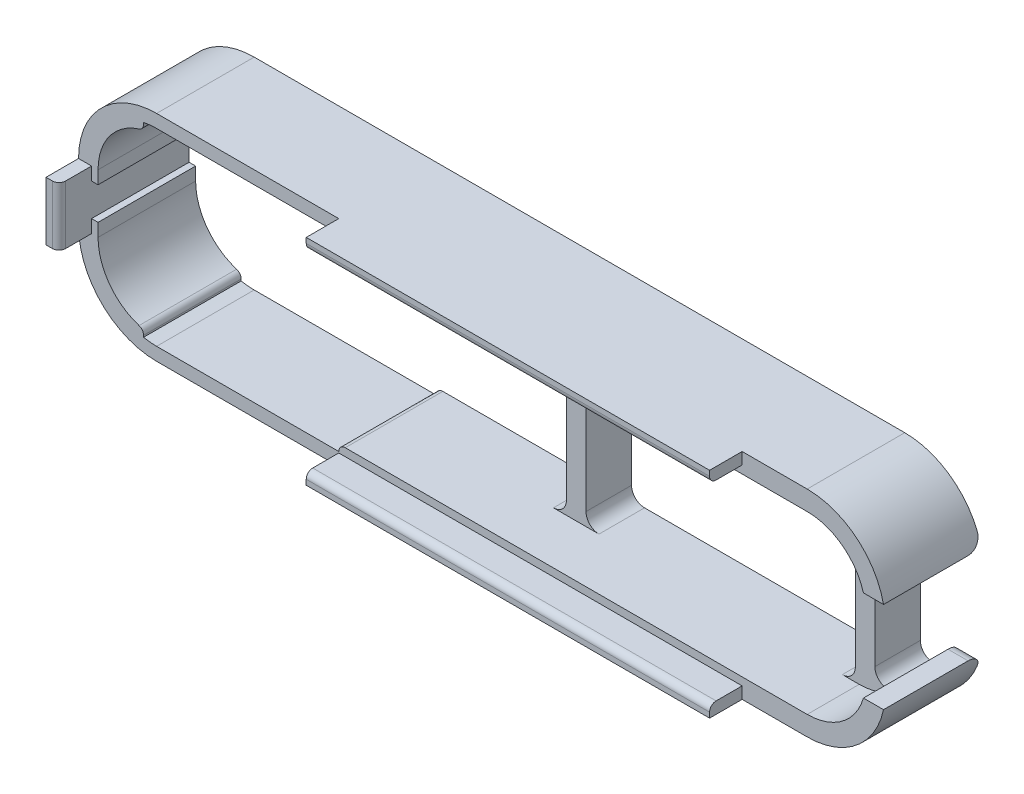
SolidWorks part; units mm, degrees
ref_plane "Front" through (0, 0, 0) normal (0, 0, 1) x (1, 0, 0)
ref_plane "Top" through (0, 0, 0) normal (0, 1, 0) x (1, 0, 0)
ref_plane "Right" through (0, 0, 0) normal (1, 0, 0) x (0, 0, -1)
sketch "Sketch1 - footprint" plane through (0, 0, 0) normal (0, 0, 1) x (1, 0, 0)
  line L1 (10, 14.5) -> (110, 14.5) construction
  line L2 (0, 4.5) -> (0, -4.5) construction
  line L3 (10, -14.5) -> (110, -14.5) construction
  line L4 (120, 4.5) -> (120, -4.5) construction
  arc A0 (110, 14.5) -> (120, 4.5) centre (110, 4.5) cw construction
  arc A1 (120, -4.5) -> (110, -14.5) centre (110, -4.5) cw construction
  arc A2 (10, -14.5) -> (0, -4.5) centre (10, -4.5) cw construction
  arc A3 (0, 4.5) -> (10, 14.5) centre (10, 4.5) cw construction
  point P4 (0, 0)
  point P8 (120, 14.5)
  point P13 (0, -14.5)
  point P16 (0, 14.5)
  dimension "D3" = 10
  dimension "D1" = 120
  dimension "D2" = 29
sketch "Sketch2" plane through (0, 0, 0) normal (0, 0, 1) x (1, 0, 0)
  line L4 (122.25, -4.5) -> (122.25, 4.5)
  line L5 (110, 16.75) -> (10, 16.75)
  line L6 (-2.25, 4.5) -> (-2.25, -4.5)
  line L7 (10, -16.75) -> (110, -16.75)
  line L8 (120.25, -4.5) -> (120.25, 4.5)
  line L9 (10, -14.75) -> (110, -14.75)
  line L10 (-0.25, 4.5) -> (-0.25, -4.5)
  line L11 (110, 14.75) -> (10, 14.75)
  line L12 (120.25, -4.5) -> (120.25, 4.5)
  line L13 (10, -14.75) -> (110, -14.75)
  line L14 (-0.25, 4.5) -> (-0.25, -4.5)
  line L15 (110, 14.75) -> (10, 14.75)
  arc A4 (122.25, 4.5) -> (110, 16.75) centre (110, 4.5) ccw
  arc A5 (10, 16.75) -> (-2.25, 4.5) centre (10, 4.5) ccw
  arc A6 (-2.25, -4.5) -> (10, -16.75) centre (10, -4.5) ccw
  arc A7 (110, -16.75) -> (122.25, -4.5) centre (110, -4.5) ccw
  arc A8 (120.25, 4.5) -> (110, 14.75) centre (110, 4.5) ccw
  arc A9 (110, -14.75) -> (120.25, -4.5) centre (110, -4.5) ccw
  arc A10 (-0.25, -4.5) -> (10, -14.75) centre (10, -4.5) ccw
  arc A11 (10, 14.75) -> (-0.25, 4.5) centre (10, 4.5) ccw
  arc A12 (120.25, 4.5) -> (110, 14.75) centre (110, 4.5) ccw
  arc A13 (110, -14.75) -> (120.25, -4.5) centre (110, -4.5) ccw
  arc A14 (-0.25, -4.5) -> (10, -14.75) centre (10, -4.5) ccw
  arc A15 (10, 14.75) -> (-0.25, 4.5) centre (10, 4.5) ccw
  dimension "D1" = 0.25
  dimension "D2" = 2
ref_plane "Plane1 - PCB bottom plane" through (0, 0, -1.6194) normal (0, 0, 1) x (1, 0, 0)
sketch "Sketch3" plane through (0, 0, -1.6194) normal (0, 0, 1) x (1, 0, 0)
  line L9 (119, -4.5) -> (119, 4.5)
  line L10 (10, -13.5) -> (110, -13.5)
  line L11 (1, 4.5) -> (1, -4.5)
  line L12 (110, 13.5) -> (10, 13.5)
  line L13 (119, -4.5) -> (119, 4.5)
  line L14 (10, -13.5) -> (110, -13.5)
  line L15 (1, 4.5) -> (1, -4.5)
  line L16 (110, 13.5) -> (10, 13.5)
  line L24 (110, 16.5) -> (10, 16.5)
  line L25 (122, -4.5) -> (122, 4.5)
  line L26 (10, -16.5) -> (110, -16.5)
  line L27 (-2, 4.5) -> (-2, -4.5)
  line L28 (110, 16.5) -> (10, 16.5)
  line L29 (122, -4.5) -> (122, 4.5)
  line L30 (10, -16.5) -> (110, -16.5)
  line L31 (-2, 4.5) -> (-2, -4.5)
  arc A8 (119, 4.5) -> (110, 13.5) centre (110, 4.5) ccw
  arc A9 (110, -13.5) -> (119, -4.5) centre (110, -4.5) ccw
  arc A10 (1, -4.5) -> (10, -13.5) centre (10, -4.5) ccw
  arc A11 (10, 13.5) -> (1, 4.5) centre (10, 4.5) ccw
  arc A12 (119, 4.5) -> (110, 13.5) centre (110, 4.5) ccw
  arc A13 (110, -13.5) -> (119, -4.5) centre (110, -4.5) ccw
  arc A14 (1, -4.5) -> (10, -13.5) centre (10, -4.5) ccw
  arc A15 (10, 13.5) -> (1, 4.5) centre (10, 4.5) ccw
  arc A23 (122, 4.5) -> (110, 16.5) centre (110, 4.5) ccw
  arc A24 (110, -16.5) -> (122, -4.5) centre (110, -4.5) ccw
  arc A25 (-2, -4.5) -> (10, -16.5) centre (10, -4.5) ccw
  arc A26 (10, 16.5) -> (-2, 4.5) centre (10, 4.5) ccw
  arc A27 (122, 4.5) -> (110, 16.5) centre (110, 4.5) ccw
  arc A28 (110, -16.5) -> (122, -4.5) centre (110, -4.5) ccw
  arc A29 (-2, -4.5) -> (10, -16.5) centre (10, -4.5) ccw
  arc A30 (10, 16.5) -> (-2, 4.5) centre (10, 4.5) ccw
  dimension "D1" = 1
  dimension "D2" = 2
extrude "Boss-Extrude2" add sketch "Sketch3" against normal blind 15
sketch "Sketch4" plane through (0, 0, -1.6194) normal (0, 0, 1) x (1, 0, 0)
  line L6 (88, -13.5) -> (88, 13.5) construction
  line L7 (10, -13.5) -> (110, -13.5) construction
  line L9 (110, 13.5) -> (10, 13.5) construction
  line L10 (120, 4.5) -> (120, -4.5) construction
  line L11 (10, -13.5) -> (110, -13.5) construction
  line L12 (109.4, -13.5) -> (112.4, -13.5)
  line L13 (109.4, -13.5) -> (109.4, 13.5)
  line L14 (109.4, 13.5) -> (112.4, 13.5)
  line L15 (112.4, -13.5) -> (112.4, 13.5)
  line L17 (65, -13.5) -> (68, -13.5)
  line L18 (65, -13.5) -> (65, 13.5)
  line L19 (65, 13.5) -> (68, 13.5)
  line L20 (68, -13.5) -> (68, 13.5)
  point P16 (120, 0)
  dimension "D1" = 32
  dimension "D2" = 3
  dimension "D3" = 7.6
  dimension "D4" = 3
  dimension "D5" = 52
  dimension "D6" = 20
extrude "Boss-Extrude4 - cross structures" add sketch "Sketch4" against normal up to surface (15 mm away) up to face at (60, 0, -16.6194)
sketch "Sketch6" plane through (0, 0, -1.6194) normal (0, 0, 1) x (1, 0, 0)
  line L0 (109.4, 13.5) -> (110, 13.5)
  line L1 (112.4, 13.1741) -> (112.4, -13.1741)
  line L2 (109.4, -13.5) -> (110, -13.5)
  line L4 (109.4, -13.5) -> (112.4, -13.5)
  line L5 (112.4, -13.5) -> (112.4, 13.5)
  line L6 (112.4, 13.5) -> (109.4, 13.5)
  line L7 (109.4, 13.5) -> (109.4, -13.5)
  line L11 (109.4, 13.5) -> (109.4, -13.5)
  line L12 (65, -13.5) -> (68, -13.5)
  line L13 (68, -13.5) -> (68, 13.5)
  line L14 (68, 13.5) -> (65, 13.5)
  line L15 (65, 13.5) -> (65, -13.5)
  line L16 (65, -13.5) -> (68, -13.5)
  line L17 (68, -13.5) -> (68, 13.5)
  line L18 (68, 13.5) -> (65, 13.5)
  line L19 (65, 13.5) -> (65, -13.5)
  arc A0 (110, 13.5) -> (112.4, 13.1741) centre (110, 4.5) cw
  arc A1 (119, 4.5) -> (112.4, 13.1741) centre (110, 4.5) ccw construction
  arc A2 (110, -13.5) -> (112.4, -13.1741) centre (110, -4.5) ccw
  arc A3 (112.4, -13.1741) -> (119, -4.5) centre (110, -4.5) ccw construction
  dimension "D1" = 0
  dimension "D2" = 0
extrude "Cut-Extrude3 - 8 mm spacing" cut sketch "Sketch6" against normal blind 8
sketch "Sketch7" plane through (0, 0, -1.6194) normal (0, 0, 1) x (1, 0, 0)
  line L0 (10, -14.5) -> (110, -14.5) construction
  line L1 (38, -14.5) -> (10, -14.5)
  line L2 (38, -14.5) -> (38, 14.5)
  line L3 (38, 14.5) -> (10, 14.5)
  line L5 (10, 14.5) -> (110, 14.5) construction
  line L6 (0, 4.5) -> (0, -4.5) construction
  line L7 (8, 14.298) -> (8, -14.298)
  arc A0 (10, 14.5) -> (0, 4.5) centre (10, 4.5) ccw construction
  arc A1 (0, -4.5) -> (10, -14.5) centre (10, -4.5) ccw construction
  arc A2 (10, -14.5) -> (8, -14.298) centre (10, -4.5) cw
  arc A3 (10, 14.5) -> (8, 14.298) centre (10, 4.5) ccw
  dimension "D1" = 38
  dimension "D2" = 30
extrude "Cut-Extrude4 - electronics spacing" cut sketch "Sketch7" against normal through all
sketch "Sketch8" plane through (122, 0, 0) normal (1, 0, 0) x (0, 0, -1)
  line L0 (1.6194, -7) -> (16.6194, -7)
  line L1 (1.6194, -4.5) -> (1.6194, -16.5) construction
  line L2 (16.6194, -7) -> (16.6194, 7)
  line L3 (16.6194, 7) -> (1.6194, 7)
  line L4 (1.6194, 16.5) -> (1.6194, 4.5) construction
  line L5 (1.6194, -7) -> (1.6194, 7)
  line L6 (16.6194, -4.5) -> (16.6194, 4.5) construction
  point P8 (1.6194, 0)
  dimension "D1" = 14
extrude "Cut-Extrude2 - USB-C cutout" cut sketch "Sketch8" against normal blind 5
sketch "Sketch10" plane through (0, 0, -1.6194) normal (0, 0, 1) x (1, 0, 0)
  line L1 (1, 1.2) -> (3, 1.2)
  line L2 (1, 1.2) -> (1, -1.2)
  line L3 (1, -1.2) -> (3, -1.2)
  line L4 (3, 1.2) -> (3, -1.2)
  line L5 (1, 4.5) -> (1, -4.5) construction
  point P6 (1, 0)
  dimension "D1" = 2.4
  dimension "D2" = 2
extrude "Boss-Extrude3" [suppressed] add sketch "Sketch10" against normal up to surface (5.5 mm away) contours L4 L3 L2 L1
sketch "Sketch11" [suppressed] plane through (0, 0, 0) normal (0, 1, 0) x (1, 0, 0)
  line L0 (3, 2.2194) -> (-2, 4.6194)
  line L1 (3, 7.1194) -> (3, 1.6194) construction
  line L2 (-2, 7.1194) -> (-2, 1.6194) construction
  line L3 (-2, 4.6194) -> (-2, 1.6194)
  line L4 (-2, 1.6194) -> (3, 1.6194)
  line L5 (3, 1.6194) -> (3, 2.2194)
  dimension "D1" = 0.6
  dimension "D2" = 3
extrude "Cut-Extrude1 - LED opening" [suppressed] cut sketch "Sketch11" against normal mid plane 2.4
fillet "Fillet4 - LED light" [suppressed] radius 1
sketch "Sketch12" plane through (0, 0, -16.6194) normal (0, 0, -1) x (-1, 0, 0)
  line L0 (-10, -16.5) -> (-110, -16.5) construction
  line L1 (-41, -16.5) -> (-51, -16.5)
  line L2 (-41, -16.5) -> (-41, -18.5)
  line L3 (-41, -18.5) -> (-51, -18.5)
  line L4 (-51, -16.5) -> (-51, -18.5)
  line L6 (-97, -16.5) -> (-107, -16.5)
  line L7 (-97, -16.5) -> (-97, -18.5)
  line L8 (-97, -18.5) -> (-107, -18.5)
  line L9 (-107, -16.5) -> (-107, -18.5)
  point P10 (-46, -16.5)
  point P12 (-102, -16.5)
  dimension "D1" = 46
  dimension "D2" = 102
  dimension "D3" = 10
  dimension "D4" = 2
extrude "Boss-Extrude4 - snap bumps" [suppressed] add sketch "Sketch12" against normal up to surface (5.5 mm away)
sketch "Sketch13" [suppressed] plane through (0, 0, -7.1194) normal (0, 0, -1) x (-1, 0, 0)
  line L0 (-51, -18.5) -> (-41, -18.5) construction
  line L1 (-43.5, -18.5) -> (-48.5, -18.5)
  line L2 (-43.5, -18.5) -> (-43.5, -14.5)
  line L3 (-43.5, -14.5) -> (-48.5, -14.5)
  line L4 (-48.5, -18.5) -> (-48.5, -14.5)
  line L6 (-107, -18.5) -> (-97, -18.5) construction
  line L7 (-99.5, -18.5) -> (-104.5, -18.5)
  line L8 (-99.5, -18.5) -> (-99.5, -14.5)
  line L9 (-99.5, -14.5) -> (-104.5, -14.5)
  line L10 (-104.5, -18.5) -> (-104.5, -14.5)
  point P8 (-46, -18.5)
  point P9 (-46, -18.5)
  point P14 (-102, -18.5)
  point P15 (-102, -18.5)
  dimension "D1" = 5
  dimension "D2" = 4
extrude "Cut-Extrude2 - snap seat (2.15, original is 2.0)" [suppressed] cut sketch "Sketch13" against normal blind 2.15
sketch "Sketch14" [suppressed] plane through (0, 0, -4.9694) normal (0, 0, -1) x (-1, 0, 0)
  line L0 (-48.5, -14.5) -> (-48.5, -18.5) construction
  line L1 (-43.5, -14.5) -> (-48.5, -14.5)
  line L2 (-43.5, -14.5) -> (-43.5, -17.35)
  line L3 (-43.5, -17.35) -> (-48.5, -17.35)
  line L4 (-48.5, -14.5) -> (-48.5, -17.35)
  line L6 (-51, -16.5) -> (-97, -16.5) construction
  line L7 (-99.5, -14.5) -> (-104.5, -14.5)
  line L8 (-99.5, -14.5) -> (-99.5, -17.35)
  line L9 (-99.5, -17.35) -> (-104.5, -17.35)
  line L10 (-104.5, -14.5) -> (-104.5, -17.35)
  line L13 (-99.5, -18.5) -> (-99.5, -14.5) construction
  dimension "D1" = 0.85
extrude "Cut-Extrude3 - snap post cut" [suppressed] cut sketch "Sketch14" against normal through all
sketch "Sketch15" [suppressed] plane through (0, 0, -7.1194) normal (0, 0, -1) x (-1, 0, 0)
  line L0 (-38, -13.5) -> (-65, -13.5) construction
  line L1 (-41, -13.5) -> (-51, -13.5)
  line L2 (-41, -13.5) -> (-41, -12.5)
  line L3 (-41, -12.5) -> (-51, -12.5)
  line L4 (-51, -13.5) -> (-51, -12.5)
  line L5 (-68, -13.5) -> (-109.4, -13.5) construction
  line L6 (-97, -13.5) -> (-107, -13.5)
  line L7 (-97, -13.5) -> (-97, -12.5)
  line L8 (-97, -12.5) -> (-107, -12.5)
  line L9 (-107, -13.5) -> (-107, -12.5)
  line L10 (-41, -18.5) -> (-41, -16.5) construction
  line L11 (-51, -16.5) -> (-51, -18.5) construction
  line L12 (-97, -18.5) -> (-97, -16.5) construction
  line L13 (-107, -16.5) -> (-107, -18.5) construction
  dimension "D1" = 1
extrude "Boss-Extrude4" [suppressed] add sketch "Sketch15" against normal up to surface (4.5 mm away)
mirror "Mirror1" [suppressed] about plane through (0, 0, 0) normal (0, 1, 0)
fillet "Fillet6 - snap features" [suppressed] radius 1
fillet "Fillet2 - USBC" radius 2 2 edges at (120.1913, 7, -16.6194) (120.1913, -7, -16.6194)
fillet "Fillet3 - inner corners, front" radius 1 4 edges at (38, 13.5, -9.1194) (38, -13.5, -9.1194) (8, -13.275, -9.1194) (8, 13.275, -9.1194)
fillet "Fillet5 - inner corners" radius 2 8 edges at (112.4, -13.1741, -13.1194) (112.4, 13.1741, -13.1194) (109.4, 13.5, -13.1194) (109.4, -13.5, -13.1194) (68, -13.5, -13.1194) (68, 13.5, -13.1194) (65, 13.5, -13.1194) (65, -13.5, -13.1194)
sketch "Sketch16" [suppressed] plane through (0, 0, -7.1194) normal (0, 0, -1) x (-1, 0, 0)
  line L0 (-98, -12.5) -> (-106, -12.5) construction
  line L1 (-109.4, -11.5) -> (-109.4, 11.5) construction
  line L2 (-98, 12.5) -> (-106, 12.5) construction
  line L3 (-97, 13.5) -> (-70, 13.5) construction
  line L4 (-70, -13.5) -> (-97, -13.5) construction
  line L5 (-68, 11.5) -> (-68, -11.5) construction
  line L6 (-38, 14.5) -> (-10, 14.5) construction
  line L7 (-41, 13.5) -> (-39, 13.5) construction
  line L8 (-42, 12.5) -> (-50, 12.5) construction
  line L9 (-63, 13.5) -> (-51, 13.5) construction
  line L10 (-65, -11.5) -> (-65, 11.5) construction
  line L11 (-51, -13.5) -> (-63, -13.5) construction
  line L12 (-42, -12.5) -> (-50, -12.5) construction
  line L13 (-39, -13.5) -> (-41, -13.5) construction
  line L14 (-10, -14.5) -> (-38, -14.5) construction
  line L15 (-98, -12.5) -> (-106, -12.5)
  line L16 (-109.4, -11.5) -> (-109.4, 11.5)
  line L17 (-98, 12.5) -> (-106, 12.5)
  line L18 (-97, 13.5) -> (-70, 13.5)
  line L19 (-70, -13.5) -> (-97, -13.5)
  line L20 (-68, 11.5) -> (-68, -11.5)
  line L21 (-38, 14.5) -> (-10, 14.5)
  line L22 (-41, 13.5) -> (-39, 13.5)
  line L23 (-42, 12.5) -> (-50, 12.5)
  line L24 (-63, 13.5) -> (-51, 13.5)
  line L25 (-65, -11.5) -> (-65, 11.5)
  line L26 (-51, -13.5) -> (-63, -13.5)
  line L27 (-42, -12.5) -> (-50, -12.5)
  line L28 (-39, -13.5) -> (-41, -13.5)
  line L29 (-10, -14.5) -> (-38, -14.5)
  line L30 (-1, -2.2) -> (-1, -4.5) construction
  line L31 (-1, -2.2) -> (-1, -4.5)
  line L32 (-1, 4.5) -> (-1, 2.2) construction
  line L33 (-1, 4.5) -> (-1, 2.2)
  line L34 (-107, -13.5) -> (-107.4, -13.5) construction
  line L35 (-107, -13.5) -> (-107.4, -13.5)
  line L36 (-107.4, 13.5) -> (-107, 13.5) construction
  line L37 (-107.4, 13.5) -> (-107, 13.5)
  line L38 (-3, -0.2) -> (-3, 0.2) construction
  line L39 (-3, -0.2) -> (-3, 0.2)
  line L40 (-8, -14.0394) -> (-8, -14.298) construction
  line L41 (-8, -14.0394) -> (-8, -14.298)
  line L42 (-8, 14.298) -> (-8, 14.0394) construction
  line L43 (-8, 14.298) -> (-8, 14.0394)
  arc A0 (-97, -13.5) -> (-98, -12.5) centre (-98, -13.5) ccw construction
  arc A1 (-106, -12.5) -> (-107, -13.5) centre (-106, -13.5) ccw construction
  arc A2 (-109.4, -11.5) -> (-107.4, -13.5) centre (-107.4, -11.5) ccw construction
  arc A3 (-107.4, 13.5) -> (-109.4, 11.5) centre (-107.4, 11.5) ccw construction
  arc A4 (-107, 13.5) -> (-106, 12.5) centre (-106, 13.5) ccw construction
  arc A5 (-98, 12.5) -> (-97, 13.5) centre (-98, 13.5) ccw construction
  arc A6 (-70, -13.5) -> (-68, -11.5) centre (-70, -11.5) ccw construction
  arc A7 (-68, 11.5) -> (-70, 13.5) centre (-70, 11.5) ccw construction
  arc A8 (-1, -2.2) -> (-2, -1.2) centre (-2, -2.2) ccw construction
  arc A9 (-3, -0.2) -> (-2, -1.2) centre (-2, -0.2) ccw construction
  arc A10 (-2, 1.2) -> (-3, 0.2) centre (-2, 0.2) ccw construction
  arc A11 (-2, 1.2) -> (-1, 2.2) centre (-2, 2.2) ccw construction
  arc A12 (-1, 4.5) -> (-7.3, 13.0855) centre (-10, 4.5) ccw construction
  arc A13 (-8, 14.0394) -> (-7.3, 13.0855) centre (-7, 14.0394) ccw construction
  arc A14 (-8, 14.298) -> (-10, 14.5) centre (-10, 4.5) ccw construction
  arc A15 (-39, 13.5) -> (-38, 14.5) centre (-39, 14.5) ccw construction
  arc A16 (-42, 12.5) -> (-41, 13.5) centre (-42, 13.5) ccw construction
  arc A17 (-51, 13.5) -> (-50, 12.5) centre (-50, 13.5) ccw construction
  arc A18 (-63, 13.5) -> (-65, 11.5) centre (-63, 11.5) ccw construction
  arc A19 (-65, -11.5) -> (-63, -13.5) centre (-63, -11.5) ccw construction
  arc A20 (-50, -12.5) -> (-51, -13.5) centre (-50, -13.5) ccw construction
  arc A21 (-41, -13.5) -> (-42, -12.5) centre (-42, -13.5) ccw construction
  arc A22 (-38, -14.5) -> (-39, -13.5) centre (-39, -14.5) ccw construction
  arc A23 (-10, -14.5) -> (-8, -14.298) centre (-10, -4.5) ccw construction
  arc A24 (-7.3, -13.0855) -> (-8, -14.0394) centre (-7, -14.0394) ccw construction
  arc A25 (-7.3, -13.0855) -> (-1, -4.5) centre (-10, -4.5) ccw construction
  arc A26 (-97, -13.5) -> (-98, -12.5) centre (-98, -13.5) ccw
  arc A27 (-106, -12.5) -> (-107, -13.5) centre (-106, -13.5) ccw
  arc A28 (-109.4, -11.5) -> (-107.4, -13.5) centre (-107.4, -11.5) ccw
  arc A29 (-107.4, 13.5) -> (-109.4, 11.5) centre (-107.4, 11.5) ccw
  arc A30 (-107, 13.5) -> (-106, 12.5) centre (-106, 13.5) ccw
  arc A31 (-98, 12.5) -> (-97, 13.5) centre (-98, 13.5) ccw
  arc A32 (-70, -13.5) -> (-68, -11.5) centre (-70, -11.5) ccw
  arc A33 (-68, 11.5) -> (-70, 13.5) centre (-70, 11.5) ccw
  arc A34 (-1, -2.2) -> (-2, -1.2) centre (-2, -2.2) ccw
  arc A35 (-3, -0.2) -> (-2, -1.2) centre (-2, -0.2) ccw
  arc A36 (-2, 1.2) -> (-3, 0.2) centre (-2, 0.2) ccw
  arc A37 (-2, 1.2) -> (-1, 2.2) centre (-2, 2.2) ccw
  arc A38 (-1, 4.5) -> (-7.3, 13.0855) centre (-10, 4.5) ccw
  arc A39 (-8, 14.0394) -> (-7.3, 13.0855) centre (-7, 14.0394) ccw
  arc A40 (-8, 14.298) -> (-10, 14.5) centre (-10, 4.5) ccw
  arc A41 (-39, 13.5) -> (-38, 14.5) centre (-39, 14.5) ccw
  arc A42 (-42, 12.5) -> (-41, 13.5) centre (-42, 13.5) ccw
  arc A43 (-51, 13.5) -> (-50, 12.5) centre (-50, 13.5) ccw
  arc A44 (-63, 13.5) -> (-65, 11.5) centre (-63, 11.5) ccw
  arc A45 (-65, -11.5) -> (-63, -13.5) centre (-63, -11.5) ccw
  arc A46 (-50, -12.5) -> (-51, -13.5) centre (-50, -13.5) ccw
  arc A47 (-41, -13.5) -> (-42, -12.5) centre (-42, -13.5) ccw
  arc A48 (-38, -14.5) -> (-39, -13.5) centre (-39, -14.5) ccw
  arc A49 (-10, -14.5) -> (-8, -14.298) centre (-10, -4.5) ccw
  arc A50 (-7.3, -13.0855) -> (-8, -14.0394) centre (-7, -14.0394) ccw
  arc A51 (-7.3, -13.0855) -> (-1, -4.5) centre (-10, -4.5) ccw
extrude "Boss-Extrude5" [suppressed] add sketch "Sketch16" against normal blind 1
sketch "Sketch17" plane through (0, 0, -16.6194) normal (0, 0, -1) x (-1, 0, 0)
  line L0 (-112.4, 9.9443) -> (-112.4, -9.9443) construction
  line L1 (-112.4, 9.9443) -> (-112.4, -9.9443)
  arc A0 (-117.7942, -9) -> (-115.6571, -11.4998) centre (-110, -4.5) ccw construction
  arc A1 (-115.6571, -11.4998) -> (-112.4, -9.9443) centre (-114.4, -9.9443) ccw construction
  arc A2 (-112.4, 9.9443) -> (-115.6571, 11.4998) centre (-114.4, 9.9443) ccw construction
  arc A3 (-115.6571, 11.4998) -> (-117.7942, 9) centre (-110, 4.5) ccw construction
  arc A4 (-117.7942, -9) -> (-115.6571, -11.4998) centre (-110, -4.5) ccw
  arc A5 (-115.6571, -11.4998) -> (-112.4, -9.9443) centre (-114.4, -9.9443) ccw
  arc A6 (-112.4, 9.9443) -> (-115.6571, 11.4998) centre (-114.4, 9.9443) ccw
  arc A7 (-115.6571, 11.4998) -> (-117.7942, 9) centre (-110, 4.5) ccw
  arc A8 (-118.6458, -7) -> (-117.7942, -9) centre (-110, -4.5) ccw construction
  arc A9 (-117.7942, 9) -> (-118.6458, 7) centre (-110, 4.5) ccw construction
  arc A10 (-118.6458, -7) -> (-117.7942, -9) centre (-110, -4.5) ccw
  arc A11 (-117.7942, 9) -> (-118.6458, 7) centre (-110, 4.5) ccw
  arc A12 (-118.6458, 7) -> (-118.6458, -7) centre (-94.4375, 0) ccw
extrude "Boss-Extrude6" [suppressed] add sketch "Sketch17" against normal blind 1
sketch "Sketch18" plane through (0, 0, -1.6194) normal (0, 0, 1) x (1, 0, 0)
  line L0 (110, 16.5) -> (10, 16.5) construction
  line L1 (38, 16.5) -> (100, 16.5)
  line L2 (38, 16.5) -> (38, 14.7)
  line L3 (38, 14.7) -> (100, 14.7)
  line L4 (100, 16.5) -> (100, 14.7)
  line L6 (10, 14.5) -> (110, 14.5) construction
  line L7 (0, 4.5) -> (0, -4.5) construction
  line L8 (10, -16.5) -> (110, -16.5) construction
  line L9 (38, -16.5) -> (100, -16.5)
  line L10 (38, -16.5) -> (38, -14.7)
  line L11 (38, -14.7) -> (100, -14.7)
  line L12 (100, -16.5) -> (100, -14.7)
  line L13 (-2, 4.5) -> (-2, -4.5) construction
  line L14 (-2, 4.5) -> (0, 4.5)
  line L15 (-2, 4.5) -> (-2, -4.5)
  line L16 (-2, -4.5) -> (0, -4.5)
  line L17 (0, 4.5) -> (0, -4.5)
  dimension "D1" = 0.2
  dimension "D2" = 62
  dimension "D3" = 38
extrude "Boss-Extrude7" add sketch "Sketch18" along normal blind 5
fillet "Fillet1" radius 1 3 edges at (69, -14.7, 3.3806) (69, 14.7, 3.3806) (0, 0, 3.3806)
sketch "Sketch19" plane through (0, 0, -1.6194) normal (0, 0, 1) x (1, 0, 0)
  line L0 (1, 4.5) -> (1, -4.5) construction
  line L1 (1, -2.5) -> (0, -2.5)
  line L2 (1, -2.5) -> (1, 2.5)
  line L3 (1, 2.5) -> (0, 2.5)
  line L4 (0, -2.5) -> (0, 2.5)
  line L5 (0, 4.5) -> (0, -4.5) construction
  point P8 (0, 0)
  dimension "D1" = 5
extrude "Cut-Extrude1" cut sketch "Sketch19" against normal through all
